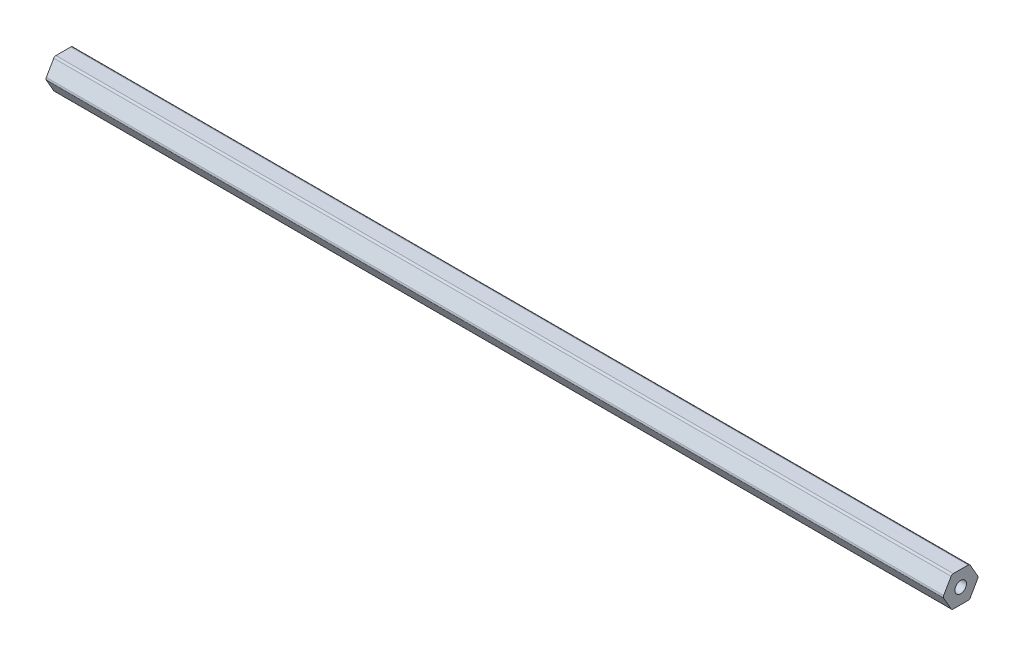
SolidWorks part; units mm, degrees
material "7075-T6 (SN)"
ref_plane "Front Plane" through (0, 0, 0) normal (0, 0, 1) x (1, 0, 0)
ref_plane "Top Plane" through (0, 0, 0) normal (0, 1, 0) x (1, 0, 0)
ref_plane "Right Plane" through (0, 0, 0) normal (1, 0, 0) x (0, 0, -1)
sketch "Sketch1" plane through (0, 0, 0) normal (1, 0, 0) x (0, 0, -1)
  line L1 (7.0391, 0.508) -> (3.9595, 5.842)
  line L2 (3.0796, 6.35) -> (-3.0796, 6.35)
  line L3 (-3.9595, 5.842) -> (-7.0391, 0.508)
  line L4 (-7.0391, -0.508) -> (-3.9595, -5.842)
  line L5 (-3.0796, -6.35) -> (3.0796, -6.35)
  line L6 (3.9595, -5.842) -> (7.0391, -0.508)
  circle A0 centre (0, 0) radius 6.35 construction
  arc A1 (3.0796, 6.35) -> (3.9595, 5.842) centre (3.0796, 5.334) cw
  arc A2 (7.0391, 0.508) -> (7.0391, -0.508) centre (6.1592, 0) cw
  arc A3 (3.9595, -5.842) -> (3.0796, -6.35) centre (3.0796, -5.334) cw
  arc A4 (-3.0796, -6.35) -> (-3.9595, -5.842) centre (-3.0796, -5.334) cw
  arc A5 (-7.0391, -0.508) -> (-7.0391, 0.508) centre (-6.1592, 0) cw
  arc A6 (-3.9595, 5.842) -> (-3.0796, 6.35) centre (-3.0796, 5.334) cw
  circle A7 centre (0, 0) radius 2.3813
  point P11 (3.6662, 6.35)
  point P14 (7.3323, 0)
  dimension "D1" = 12.7
  dimension "D3" = 1.016
  dimension "D4" = 4.7625
  dimension "D2" = 6.35
extrude "Boss-Extrude1" add sketch "Sketch1" along normal blind 371.475
